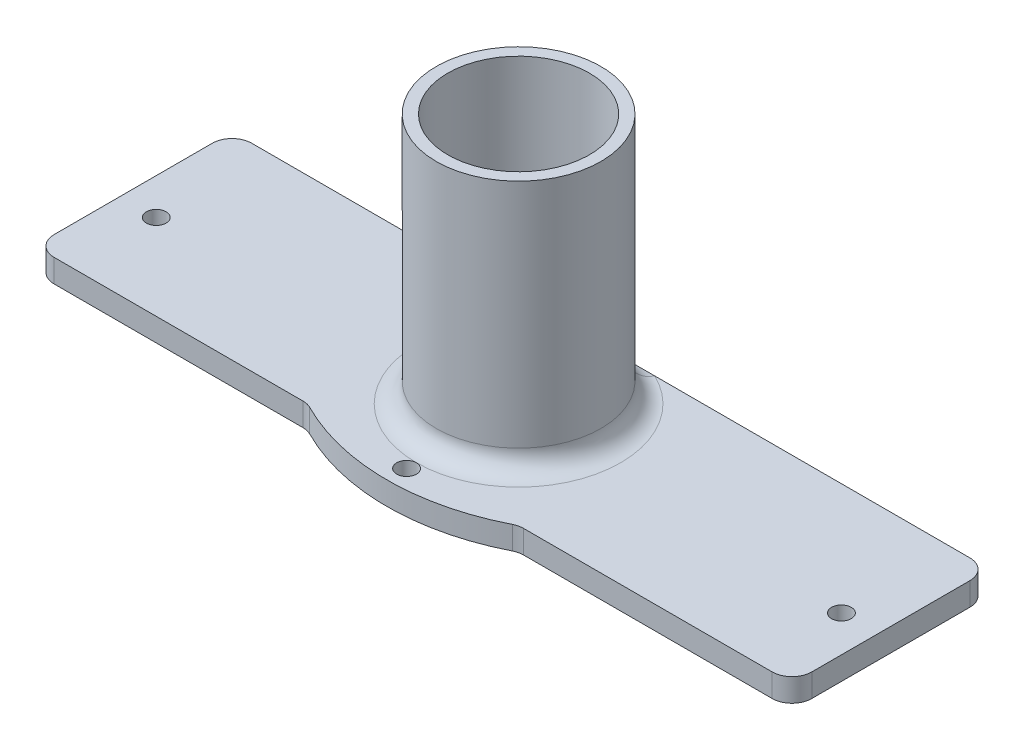
SolidWorks part; units mm, degrees
ref_plane "Front Plane" through (0, 0, 0) normal (0, 0, 1) x (1, 0, 0)
ref_plane "Top Plane" through (0, 0, 0) normal (0, 1, 0) x (1, 0, 0)
ref_plane "Right Plane" through (0, 0, 0) normal (1, 0, 0) x (0, 0, -1)
sketch "Sketch1" plane through (0, 0, 0) normal (1, 0, 0) x (0, 0, -1)
  line L9 (0, 0) -> (30, 0)
  line L10 (0, 0) -> (0, -3.5)
  line L12 (30, 0) -> (30, -3.5)
  line L13 (0, -3.5) -> (30, -3.5)
  dimension "D2" = 3.5
  dimension "D4" = 30
extrude "Boss-Extrude1" add sketch "Sketch1" along normal blind 115
sketch "Sketch6" plane through (0, 0, 0) normal (0, 1, 0) x (1, 0, 0)
  line L0 (115, 0) -> (0, 0) construction
  line L1 (115, 0) -> (0, 0) construction
  line L2 (115, 30) -> (0, 30) construction
  line L3 (41.5, 0) -> (73.5, 0)
  arc A0 (41.5, 0) -> (73.5, 0) centre (57.5, 30) ccw
  point P12 (57.5, -4)
  point P14 (57.5, 30)
  dimension "D1" = 32
extrude "Boss-Extrude4" add sketch "Sketch6" against normal up to surface (3.5 mm away) up to face at (57.5, -3.5, -15)
sketch "Sketch3" plane through (0, 0, 0) normal (0, 1, 0) x (1, 0, 0)
  line L0 (57.5, -1) -> (5.5, 13) construction
  line L1 (5.5, 13) -> (109.5, 13) construction
  line L2 (109.5, 13) -> (57.5, -1) construction
  line L3 (5.5, 13) -> (0, 13) construction
  line L4 (0, 30) -> (0, 0) construction
  line L5 (109.5, 13) -> (115, 13) construction
  line L6 (115, 30) -> (115, 0) construction
  line L7 (115, 0) -> (73.5, 0) construction
  circle A0 centre (57.5, -1) radius 1.5
  circle A1 centre (109.5, 13) radius 1.5
  circle A2 centre (5.5, 13) radius 1.5
  dimension "D4" = 3
  dimension "D1" = 1
  dimension "D2" = 13
  dimension "D3" = 104
extrude "Cut-Extrude2" cut sketch "Sketch3" against normal through all and the other way through all
sketch "Sketch5" plane through (0, 0, 0) normal (0, 1, 0) x (1, 0, 0)
  line L0 (115, 30) -> (0, 30) construction
  circle A0 centre (57.5, 16) radius 12.5
  circle A1 centre (57.5, 16) radius 10.75
  point P7 (57.5, 30)
  dimension "D1" = 21.5
  dimension "D2" = 25
  dimension "D3" = 14
extrude "Boss-Extrude3" add sketch "Sketch5" along normal blind 38.1
fillet "Fillet2" radius 3 1 edges at (57.5, 0, -28.5)
fillet "Fillet3" radius 3 6 edges at (115, -1.75, -30) (115, -1.75, 0) (73.5, -1.75, 0) (41.5, -1.75, 0) (0, -1.75, 0) (0, -1.75, -30)
